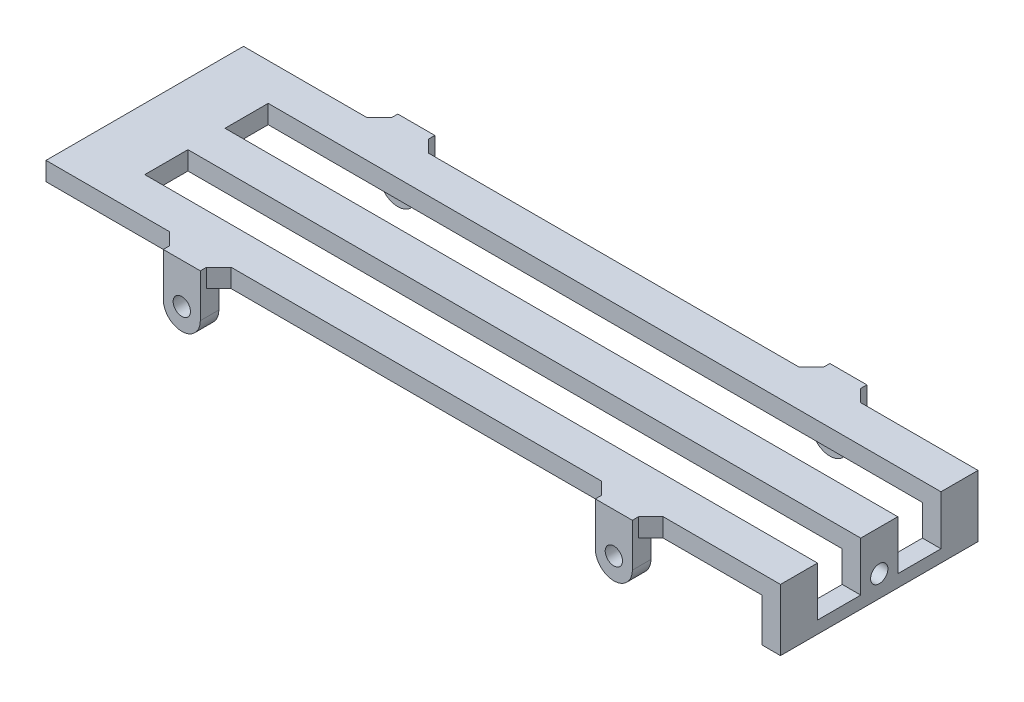
SolidWorks part; units mm, degrees
ref_plane "Front Plane" through (0, 0, 0) normal (0, 0, 1) x (1, 0, 0)
ref_plane "Top Plane" through (0, 0, 0) normal (0, 1, 0) x (1, 0, 0)
ref_plane "Right Plane" through (0, 0, 0) normal (1, 0, 0) x (0, 0, -1)
sketch "Sketch1" plane through (0, 0, 0) normal (0, 1, 0) x (1, 0, 0)
  line L0 (0, 0) -> (27.1615, 0) construction
  line L1 (-59.5, 16) -> (59.5, 16)
  line L2 (-59.5, 16) -> (-59.5, -16)
  line L3 (-59.5, -16) -> (59.5, -16)
  line L4 (59.5, 16) -> (59.5, -16)
  line L5 (-59.5, 16) -> (59.5, -16) construction
  line L6 (-59.5, -16) -> (59.5, 16) construction
  line L7 (-49.5, 10) -> (55.5, 10)
  line L8 (-49.5, 10) -> (-49.5, 3)
  line L9 (-49.5, 3) -> (55.5, 3)
  line L10 (55.5, 10) -> (55.5, 3)
  line L11 (-49.5, 10) -> (55.5, 3) construction
  line L12 (-49.5, 3) -> (55.5, 10) construction
  line L13 (55.5, -10) -> (55.5, -3)
  line L14 (-49.5, -3) -> (55.5, -3)
  line L15 (-49.5, -10) -> (-49.5, -3)
  line L16 (-49.5, -10) -> (55.5, -10)
  point P0 (0, 0)
  point P5 (3, 6.5)
  dimension "D1" = 32
  dimension "D2" = 119
  dimension "D3" = 4
  dimension "D4" = 6
  dimension "D5" = 7
  dimension "105" = 105
extrude "Boss-Extrude1" add sketch "Sketch1" along normal blind 3
sketch "Sketch2" plane through (0, 0, 16) normal (0, 0, 1) x (1, 0, 0)
  line L0 (-59.5, 0) -> (59.5, 0) construction
  line L1 (32.5, -7) -> (38.5, -7)
  line L2 (32.5, -7) -> (32.5, 0)
  line L3 (32.5, 0) -> (38.5, 0)
  line L4 (38.5, -7) -> (38.5, 0)
  line L5 (32.5, -7) -> (38.5, 0) construction
  line L6 (32.5, 0) -> (38.5, -7) construction
  line L7 (59.5, 3) -> (59.5, 0) construction
  line L8 (-59.5, 3) -> (59.5, 3) construction
  line L9 (32.5, 0) -> (38.5, 0)
  line L10 (32.5, 0) -> (32.5, 3)
  line L11 (32.5, 3) -> (38.5, 3)
  line L12 (38.5, 0) -> (38.5, 3)
  line L13 (0.5, 0) -> (0.5, -5.6474) construction
  line L14 (-31.5, 0) -> (-37.5, -7) construction
  line L15 (-31.5, -7) -> (-37.5, 0) construction
  line L16 (-37.5, 0) -> (-37.5, 3)
  line L17 (-31.5, 3) -> (-37.5, 3)
  line L18 (-31.5, 0) -> (-31.5, 3)
  line L19 (-31.5, 0) -> (-37.5, 0)
  line L20 (-37.5, -7) -> (-37.5, 0)
  line L21 (-31.5, 0) -> (-37.5, 0)
  line L22 (-31.5, -7) -> (-31.5, 0)
  line L23 (-31.5, -7) -> (-37.5, -7)
  circle A2 centre (35.5, -3.5) radius 1.4
  circle A3 centre (-34.5, -3.5) radius 1.4
  point P0 (35.5, -3.5)
  point P26 (-34.5, -3.5)
  line M3 (-59.5, 0) -> (59.5, 0)
  line M5 (59.5, 3) -> (-59.5, 3)
  dimension "D3" = 2.8
  dimension "D1" = 24
  dimension "D2" = 7
  dimension "D5" = 6
  dimension "D6" = 35
extrude "Boss-Extrude2" add sketch "Sketch2" along normal blind 3 contours L1 L4 L2 A2 M3 | L12 L10 M3 M5 | L23 L22 L20 A3 M3 | L18 L16 M3 M5 region at (32.5922, -3.5, 16) region at (35.5, 1.5, 16) region at (-34.5, 1.5, 16) region at (-31.5922, -3.5, 16)
mirror "Mirror4" about plane through (0, 0, 0) normal (0, 0, 1) of "Boss-Extrude2"
chamfer "Chamfer1" distance 2 angle 45 8 edges at (32.5, 1.5, 16) (38.5, 1.5, 16) (-31.5, 1.5, 16) (-37.5, 1.5, 16) (32.5, 1.5, -16) (38.5, 1.5, -16) (-31.5, 1.5, -16) (-37.5, 1.5, -16)
fillet "Fillet1" radius 3 8 edges at (32.5, -7, -17.5) (38.5, -7, -17.5) (32.5, -7, 17.5) (38.5, -7, 17.5) (-37.5, -7, -17.5) (-31.5, -7, -17.5) (-31.5, -7, 17.5) (-37.5, -7, 17.5)
sketch "Sketch3" plane through (0, 0, -16) normal (0, 0, -1) x (-1, 0, 0)
  line L1 (-59.5, 3) -> (-56.5, 3)
  line L2 (-59.5, 3) -> (-59.5, -11)
  line L3 (-59.5, -11) -> (-56.5, -11)
  line L4 (-56.5, 3) -> (-56.5, -11)
  line M3 (-59.5, 0) -> (-40.5, 0)
  dimension "D1" = 3
  dimension "D2" = 14
extrude "Boss-Extrude4" add sketch "Sketch3" against normal up to surface (32 mm away) contours L4 L2 L3 M3 region at (58, -5.5, -16) up to face at (50, 1.5, 16)
sketch "Sketch4" plane through (0, 3, 0) normal (0, 1, 0) x (1, 0, 0)
  line L0 (59.5, -16) -> (59.5, 16) construction
  line L1 (55.5, 10) -> (59.5, 10)
  line L2 (55.5, 10) -> (55.5, 3)
  line L3 (55.5, 3) -> (59.5, 3)
  line L4 (59.5, 10) -> (59.5, 3)
  line L6 (55.5, -3) -> (59.5, -3)
  line L7 (55.5, -3) -> (55.5, -10)
  line L8 (55.5, -10) -> (59.5, -10)
  line L9 (59.5, -3) -> (59.5, -10)
extrude "Cut-Extrude1" cut sketch "Sketch4" against normal offset from surface (8 mm away) 6 up to face at (58, -11, 0)
sketch "Sketch5" plane through (59.5, 0, 0) normal (1, 0, 0) x (0, 0, -1)
  line L0 (-3, 3) -> (3, 3) construction
  circle A0 centre (0, -3.5) radius 1.4
  dimension "D1" = 2.8
  dimension "D2" = 6.5
extrude "Cut-Extrude2" cut sketch "Sketch5" against normal through all
sketch "Sketch6" plane through (59.5, 0, 0) normal (1, 0, 0) x (0, 0, -1)
  line L0 (16, 3) -> (16, -11) construction
  line L1 (-16, -11) -> (16, -11)
  line L2 (-16, -11) -> (-16, -7)
  line L3 (-16, -7) -> (16, -7)
  line L4 (16, -11) -> (16, -7)
  dimension "D1" = 7
extrude "Cut-Extrude3" cut sketch "Sketch6" against normal blind 10
